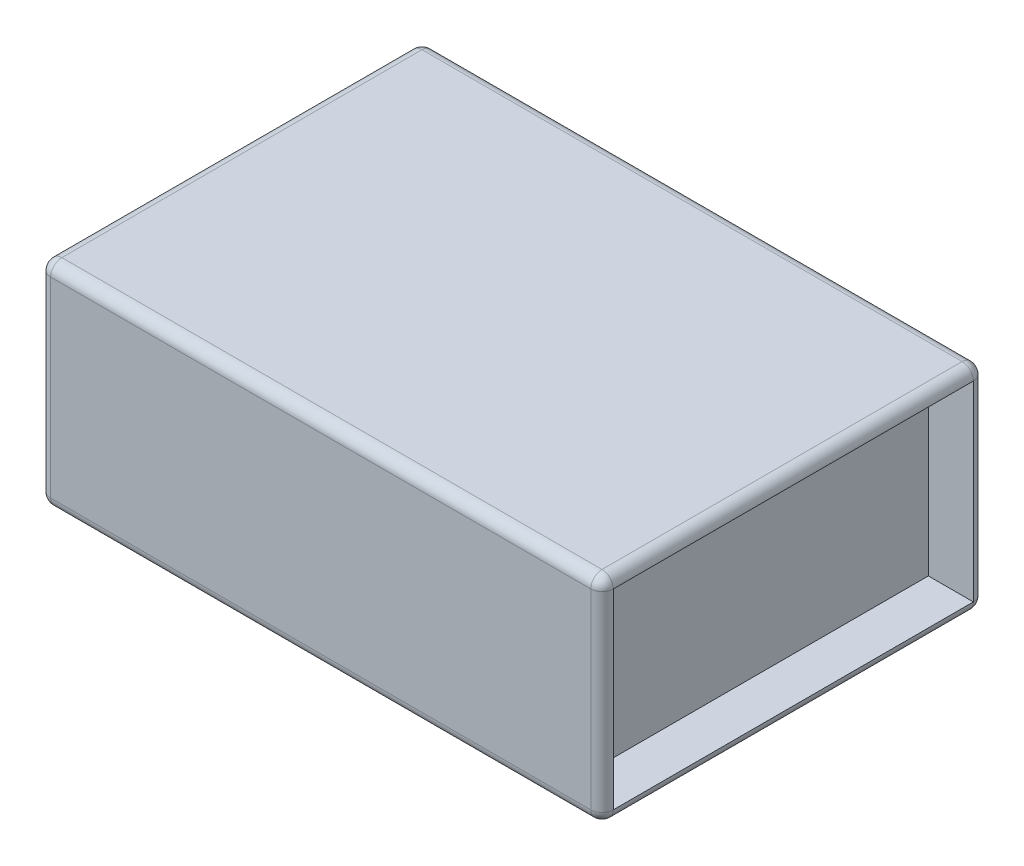
SolidWorks part; units mm, degrees
ref_plane "Front" through (0, 0, 0) normal (0, 0, 1) x (1, 0, 0)
ref_plane "Top" through (0, 0, 0) normal (0, 1, 0) x (1, 0, 0)
ref_plane "Right" through (0, 0, 0) normal (1, 0, 0) x (0, 0, -1)
sketch "Sketch1" plane through (0, 0, 0) normal (0, 1, 0) x (1, 0, 0)
  line L1 (-25, 17) -> (25, 17)
  line L2 (-25, 17) -> (-25, -17)
  line L3 (-25, -17) -> (25, -17)
  line L4 (25, 17) -> (25, -17)
  line L5 (-25, 17) -> (25, -17) construction
  line L6 (-25, -17) -> (25, 17) construction
  point P0 (0, 0)
  dimension "D1" = 34
  dimension "D2" = 50
extrude "Boss-Extrude1" add sketch "Sketch1" along normal blind 19
sketch "Sketch2" plane through (25, 0, 0) normal (1, 0, 0) x (0, 0, -1)
  line L24 (-16, 18) -> (-16, 1)
  line L25 (-16, 1) -> (16, 1)
  line L26 (16, 18) -> (-16, 18)
  line L27 (16, 1) -> (16, 18)
  line L28 (-16, 18) -> (-16, 1)
  line L29 (-16, 1) -> (16, 1)
  line L30 (16, 18) -> (-16, 18)
  line L31 (16, 1) -> (16, 18)
  dimension "D1" = 1
extrude "Cut-Extrude1" cut sketch "Sketch2" against normal blind 4
fillet "Fillet1" radius 1 10 edges at (-25, 0, 0) (0, 0, 17) (0, 0, -17) (25, 0, 0) (-25, 19, 0) (0, 19, 17) (0, 19, -17) (25, 19, 0) (25, 9.5, 17) (25, 9.5, -17)
fillet "Fillet2" radius 1 6 edges at (-24.7071, 18.7071, -16.7071) (-24.7071, 0.2929, -16.7071) (-24.7071, 18.7071, 16.7071) (-24.7071, 0.2929, 16.7071) (-25, 9.5, -17) (-25, 9.5, 17)
